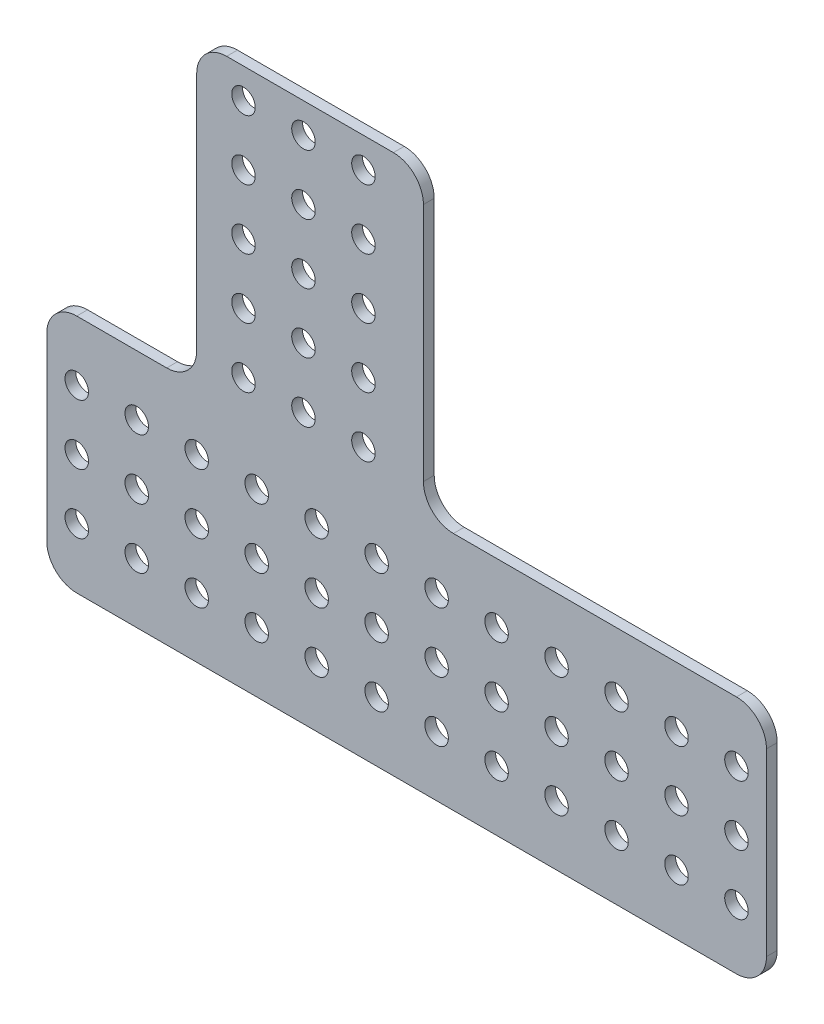
SolidWorks part; units mm, degrees
ref_plane "Front Plane" through (0, 0, 0) normal (0, 0, 1) x (1, 0, 0)
ref_plane "Top Plane" through (0, 0, 0) normal (0, 1, 0) x (1, 0, 0)
ref_plane "Right Plane" through (0, 0, 0) normal (1, 0, 0) x (0, 0, -1)
sketch "Sketch1" plane through (0, 0, 0) normal (0, 0, 1) x (1, 0, 0)
  line L0 (-255.429, 188.8429) -> (-220.1184, 188.8429)
  line L1 (-213.7684, 182.4929) -> (-213.7684, 131.6929)
  line L2 (-207.4184, 125.3429) -> (-147.479, 125.3429)
  line L3 (-141.129, 118.9929) -> (-141.129, 80.8929)
  line L4 (-147.479, 74.5429) -> (-287.179, 74.5429)
  line L5 (-293.529, 80.8929) -> (-293.529, 118.9929)
  line L6 (-287.179, 125.3429) -> (-268.129, 125.3429)
  line L7 (-261.779, 131.6929) -> (-261.779, 182.4929)
  line L8 (-264.5684, 125.3429) -> (-213.7684, 125.3429) construction
  line L9 (-213.7684, 811.1429) -> (-213.7684, 125.3429) construction
  line L10 (-287.179, 112.6429) -> (-274.479, 112.6429) construction
  line L11 (-287.179, 112.6429) -> (-287.179, 99.9429) construction
  arc A0 (-268.129, 125.3429) -> (-261.779, 131.6929) centre (-268.129, 131.6929) ccw
  arc A1 (-293.529, 118.9929) -> (-287.179, 125.3429) centre (-287.179, 118.9929) cw
  arc A2 (-287.179, 74.5429) -> (-293.529, 80.8929) centre (-287.179, 80.8929) cw
  arc A3 (-141.129, 80.8929) -> (-147.479, 74.5429) centre (-147.479, 80.8929) cw
  arc A4 (-147.479, 125.3429) -> (-141.129, 118.9929) centre (-147.479, 118.9929) cw
  arc A5 (-213.7684, 131.6929) -> (-207.4184, 125.3429) centre (-207.4184, 131.6929) ccw
  arc A6 (-255.429, 188.8429) -> (-261.779, 182.4929) centre (-255.429, 182.4929) ccw
  arc A7 (-220.1184, 188.8429) -> (-213.7684, 182.4929) centre (-220.1184, 182.4929) cw
  circle A8 centre (-226.4684, 182.4929) radius 2.4892 construction
  circle A9 centre (-226.4684, 157.0929) radius 2.4892 construction
  circle A10 centre (-226.4684, 144.3929) radius 2.4892 construction
  circle A11 centre (-226.4684, 131.6929) radius 2.4892 construction
  circle A12 centre (-239.1684, 131.6929) radius 2.4892 construction
  circle A13 centre (-251.8684, 131.6929) radius 2.4892 construction
  circle A14 centre (-251.8684, 144.3929) radius 2.4892 construction
  circle A15 centre (-239.1684, 144.3929) radius 2.4892 construction
  circle A16 centre (-239.1684, 157.0929) radius 2.4892 construction
  circle A17 centre (-251.8684, 157.0929) radius 2.4892 construction
  circle A18 centre (-226.4684, 169.7929) radius 2.4892 construction
  circle A19 centre (-239.1684, 182.4929) radius 2.4892 construction
  circle A20 centre (-239.1684, 169.7929) radius 2.4892 construction
  circle A21 centre (-251.8684, 169.7929) radius 2.4892 construction
  circle A22 centre (-251.8684, 182.4929) radius 2.4892 construction
  circle A23 centre (-226.4684, 157.0929) radius 2.4892
  circle A24 centre (-226.4684, 144.3929) radius 2.4892
  circle A25 centre (-226.4684, 131.6929) radius 2.4892
  circle A26 centre (-239.1684, 131.6929) radius 2.4892
  circle A27 centre (-251.8684, 131.6929) radius 2.4892
  circle A28 centre (-251.8684, 144.3929) radius 2.4892
  circle A29 centre (-239.1684, 144.3929) radius 2.4892
  circle A30 centre (-239.1684, 157.0929) radius 2.4892
  circle A31 centre (-251.8684, 157.0929) radius 2.4892
  circle A32 centre (-226.4684, 169.7929) radius 2.4892
  circle A33 centre (-226.4684, 182.4929) radius 2.4892
  circle A34 centre (-239.1684, 182.4929) radius 2.4892
  circle A35 centre (-239.1684, 169.7929) radius 2.4892
  circle A36 centre (-251.8684, 169.7929) radius 2.4892
  circle A37 centre (-251.8684, 182.4929) radius 2.4892
  circle A38 centre (-287.179, 112.6429) radius 2.4892
  circle A39 centre (-274.479, 112.6429) radius 2.4892
  circle A40 centre (-261.779, 112.6429) radius 2.4892
  circle A41 centre (-249.079, 112.6429) radius 2.4892
  circle A42 centre (-236.379, 112.6429) radius 2.4892
  circle A43 centre (-223.679, 112.6429) radius 2.4892
  circle A44 centre (-210.979, 112.6429) radius 2.4892
  circle A45 centre (-198.279, 112.6429) radius 2.4892
  circle A46 centre (-185.579, 112.6429) radius 2.4892
  circle A47 centre (-172.879, 112.6429) radius 2.4892
  circle A48 centre (-160.179, 112.6429) radius 2.4892
  circle A49 centre (-147.479, 112.6429) radius 2.4892
  circle A50 centre (-274.479, 99.9429) radius 2.4892
  circle A51 centre (-261.779, 99.9429) radius 2.4892
  circle A52 centre (-249.079, 99.9429) radius 2.4892
  circle A53 centre (-236.379, 99.9429) radius 2.4892
  circle A54 centre (-223.679, 99.9429) radius 2.4892
  circle A55 centre (-210.979, 99.9429) radius 2.4892
  circle A56 centre (-198.279, 99.9429) radius 2.4892
  circle A57 centre (-185.579, 99.9429) radius 2.4892
  circle A58 centre (-172.879, 99.9429) radius 2.4892
  circle A59 centre (-160.179, 99.9429) radius 2.4892
  circle A60 centre (-147.479, 99.9429) radius 2.4892
  circle A61 centre (-274.479, 87.2429) radius 2.4892
  circle A62 centre (-261.779, 87.2429) radius 2.4892
  circle A63 centre (-249.079, 87.2429) radius 2.4892
  circle A64 centre (-236.379, 87.2429) radius 2.4892
  circle A65 centre (-223.679, 87.2429) radius 2.4892
  circle A66 centre (-210.979, 87.2429) radius 2.4892
  circle A67 centre (-198.279, 87.2429) radius 2.4892
  circle A68 centre (-185.579, 87.2429) radius 2.4892
  circle A69 centre (-172.879, 87.2429) radius 2.4892
  circle A70 centre (-160.179, 87.2429) radius 2.4892
  circle A71 centre (-147.479, 87.2429) radius 2.4892
  circle A72 centre (-287.179, 99.9429) radius 2.4892
  circle A73 centre (-287.179, 87.2429) radius 2.4892
  point P76 (0, 0)
  point P77 (0, 0)
  point P150 (0, 0)
  point P151 (0, 0)
  dimension "D2" = 6.35
  dimension "D6" = 12.7
  dimension "D8" = 4.9784
  dimension "D9" = 12
  dimension "D4" = 6.35
  dimension "D1" = 6.35
  dimension "D3" = 152.4
  dimension "D5" = 50.8
  dimension "D7" = 31.75
  dimension "D11" = 12.7
  dimension "D12" = 12.7
  dimension "D10" = 3
extrude "Boss-Extrude1" add sketch "Sketch1" along normal blind 2.286
